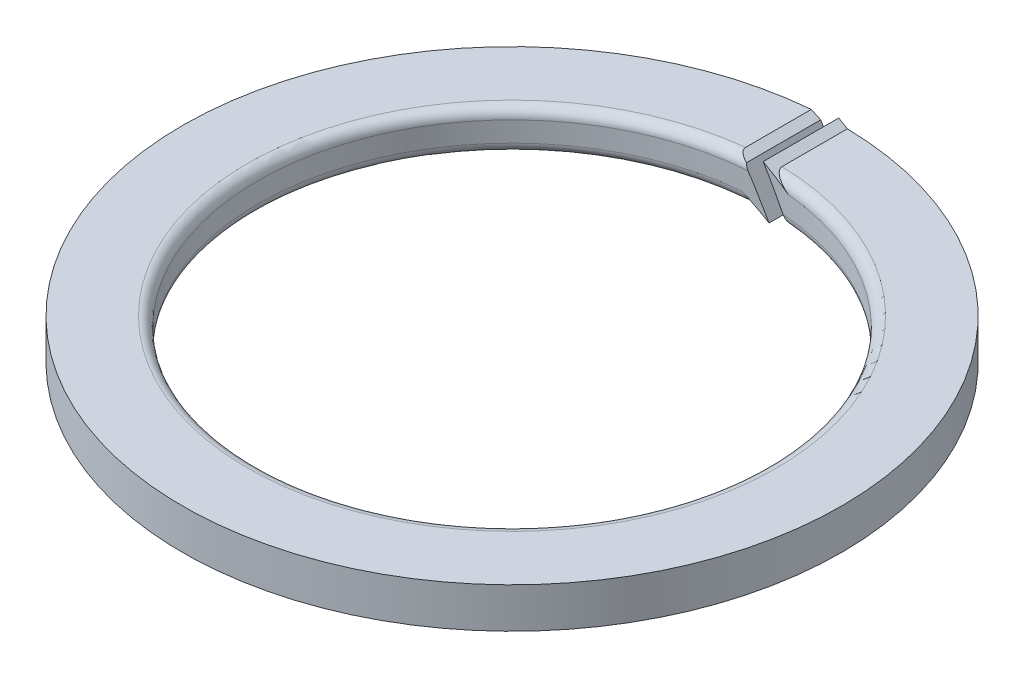
SolidWorks part; units mm, degrees
ref_plane "Front Plane" through (0, 0, 0) normal (0, 0, 1) x (1, 0, 0)
ref_plane "Top Plane" through (0, 0, 0) normal (0, 1, 0) x (1, 0, 0)
ref_plane "Right Plane" through (0, 0, 0) normal (1, 0, 0) x (0, 0, -1)
sketch "BodySke" plane through (0, 0, 0) normal (0, 0, 1) x (1, 0, 0)
  line L0 (0, 0) -> (0, 99.9596) construction
  line L1 (0, 0) -> (50.5, 0) construction
  line L3 (50.5, -10) -> (65.5, -10)
  line L4 (50.5, -10) -> (50.5, 10)
  line L5 (50.5, 10) -> (65.5, 10)
  line L6 (65.5, -10) -> (65.5, 10)
  line L7 (50.5, -4) -> (65.5, -4) construction
  line L8 (50.5, -4) -> (50.5, 4) construction
  line L9 (50.5, 4) -> (65.5, 4) construction
  line L10 (65.5, -4) -> (65.5, 4) construction
  dimension "Inner_dia" = 101
  dimension "Outer_dia" = 131
  dimension "D3" = 20
  dimension "Thickness" = 8
revolve "BaseBody" add sketch "BodySke" angle 360 about L0
sketch "Cut-ExtraSke" plane through (0, 0, 0) normal (0, 0, 1) x (1, 0, 0)
  line L1 (65.5, -4) -> (-65.5, -4)
  line L2 (65.5, -4) -> (65.5, -10)
  line L3 (65.5, -10) -> (-65.5, -10)
  line L4 (-65.5, -4) -> (-65.5, -10)
  line L5 (65.5, 4) -> (-65.5, 4)
  line L6 (65.5, 4) -> (65.5, 10)
  line L7 (65.5, 10) -> (-65.5, 10)
  line L8 (-65.5, 4) -> (-65.5, 10)
extrude "Cut-Extra" cut sketch "Cut-ExtraSke" along normal through all
sketch "ASke" plane through (0, 0, 0) normal (0, 0, 1) x (1, 0, 0)
  line L0 (0, -16.7192) -> (0, 28.802) construction
  line L1 (65.5, 4) -> (-65.5, 4) construction
  line L2 (0.5774, -5) -> (-4.6188, 4) construction
  line L4 (0.5774, -5) -> (-1.1547, -4)
  line L7 (-5.7735, 4) -> (-4.0415, 3)
  line L8 (-0.5774, 5) -> (4.6188, -4) construction
  line L9 (4.0415, -3) -> (5.7735, -4)
  line L10 (-65.5, 10) -> (65.5, 10)
  line L11 (-0.5774, 5) -> (1.1547, 4)
  line L12 (65.5, -4) -> (-65.5, -4) construction
  line L13 (65.5, 10) -> (65.5, 4)
  line L14 (65.5, 4) -> (1.1547, 4)
  line L15 (5.7735, -4) -> (65.5, -4)
  line L16 (65.5, -4) -> (65.5, -10)
  line L17 (65.5, -10) -> (-65.5, -10)
  line L18 (-65.5, -10) -> (-65.5, -4)
  line L19 (-65.5, -4) -> (-1.1547, -4)
  line L20 (0.5774, -5) -> (-4.0415, 3)
  line L21 (4.0415, -3) -> (-0.5774, 5)
  line L22 (-5.7735, 4) -> (-65.5, 4)
  line L23 (-65.5, 4) -> (-65.5, 10)
  line L24 (-65.5, 10) -> (-65.5, 4) construction
  line L25 (-65.5, -4) -> (-65.5, -10) construction
  line L26 (50.5, 10) -> (65.5, 10) construction
  line L27 (50.5, -10) -> (65.5, -10) construction
  point P11 (0, -4)
  point P12 (0, 4)
  dimension "D4" = 1
  dimension "D5" = 1
  dimension "D6" = 1
extrude "Type-A" cut sketch "ASke" against normal through all
sketch "BSke" plane through (0, 0, 0) normal (0, 0, 1) x (1, 0, 0)
  line L0 (0, 0) -> (0, 31.0126) construction
  line L1 (0, 0) -> (0, 99.9596) construction
  line L2 (0, -4) -> (-4.6188, 4)
  line L3 (65.5, 4) -> (-65.5, 4) construction
  line L4 (0, 4) -> (4.6188, -4)
  line L5 (-65.5, -4) -> (65.5, -4) construction
  line L6 (-50.5, -4) -> (50.5, -4) construction
  line L7 (0, -4) -> (-65.5, -4)
  line L8 (-65.5, -4) -> (-65.5, -10)
  line L9 (-65.5, -10) -> (65.5, -10)
  line L10 (65.5, -10) -> (65.5, -4)
  line L11 (65.5, -4) -> (4.6188, -4)
  line L12 (0, 4) -> (65.5, 4)
  line L13 (65.5, 4) -> (65.5, 10)
  line L14 (65.5, 10) -> (-65.5, 10)
  line L15 (-65.5, 10) -> (-65.5, 4)
  line L16 (-65.5, 4) -> (-4.6188, 4)
  line L17 (-65.5, 4) -> (-65.5, -4) construction
  dimension "Angle" = 30
extrude "Type-B" [suppressed] cut sketch "BSke" against normal through all
fillet "Fillet1" radius 2 2 edges at (-2.3149, -4, 50.4469) (2.3149, 4, 50.4469)
equation "\"D4@ASke\" = \"Offset@ASke\""
equation "\"D5@ASke\" = \"Offset@ASke\""
equation "\"D6@ASke\" = \"Offset@ASke\""
